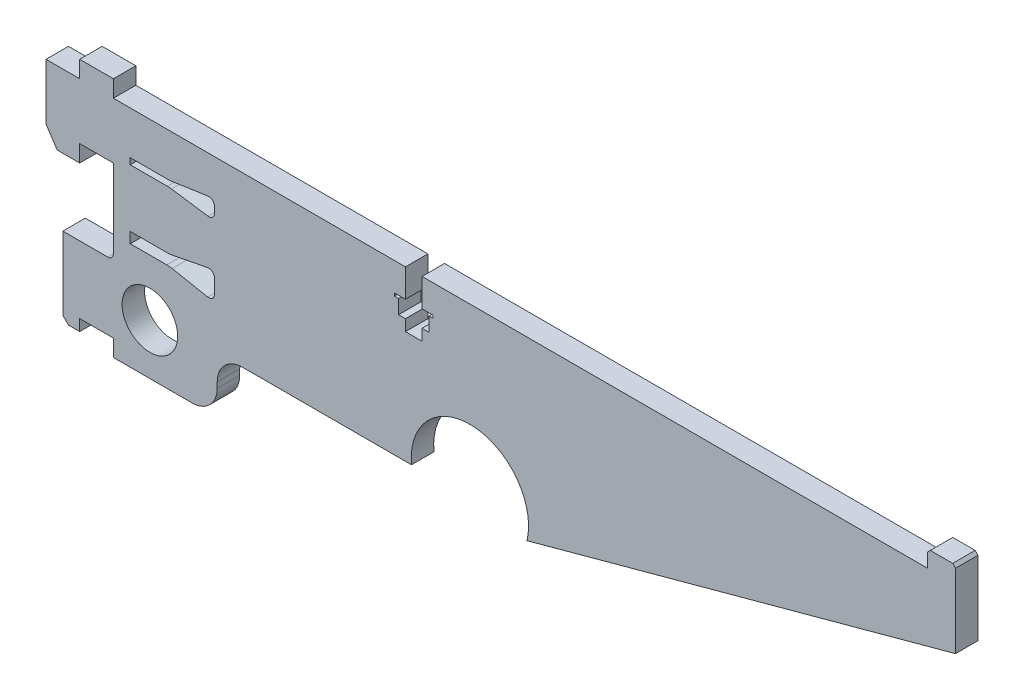
SolidWorks part; units mm, degrees
material "Oak"
ref_plane "Front Plane" through (0, 0, 0) normal (0, 0, 1) x (1, 0, 0)
ref_plane "Top Plane" through (0, 0, 0) normal (0, 1, 0) x (1, 0, 0)
ref_plane "Right Plane" through (0, 0, 0) normal (1, 0, 0) x (0, 0, -1)
sketch "Sketch1" plane through (0, 0, 0) normal (0, 0, 1) x (1, 0, 0)
  line L0 (7.5, -7) -> (16.5, -7)
  line L1 (16.5, -7) -> (16.5, 8)
  line L2 (16.5, 8) -> (10.5, 8)
  line L3 (10.5, 8) -> (10.5, 5)
  line L4 (10.5, 5) -> (4.5, 5)
  line L5 (4.5, 5) -> (4.5, 18)
  line L6 (4.5, 18) -> (10.5, 18)
  line L7 (166.5, 21) -> (166.5, 7.3204)
  line L8 (72.4558, -18.231) -> (90.1661, -13.4192) construction
  line L9 (10.5, -21) -> (7.5, -21)
  line L10 (-18, 24.8801) -> (-18, -27.1715) construction
  line L11 (10.5, 18) -> (10.5, 21)
  line L12 (10.5, 21) -> (16.5, 21)
  line L13 (19.5, -2) -> (34.5, -2) construction
  line L14 (19.5, -2.95) -> (19.5, -1.05)
  line L15 (19.5, -1.05) -> (26.5, -1.05)
  line L16 (26.5, -1.05) -> (34.5, 0.5)
  line L17 (34.5, 0.5) -> (34.5, -4.5)
  line L18 (26.5, -2.95) -> (34.5, -4.5)
  line L19 (19.5, -2.95) -> (26.5, -2.95)
  line L20 (19.5, -13) -> (34.5, -13) construction
  line L21 (19.5, -16.5) -> (19.5, -9.5) construction
  line L22 (19.5, -9.5) -> (34.5, -9.5) construction
  line L23 (16.5, -22) -> (16.5, -19)
  line L24 (34.5, -9.5) -> (34.5, -16.5) construction
  line L25 (16.5, -19) -> (10.5, -19)
  line L26 (19.5, -16.5) -> (34.5, -16.5) construction
  line L27 (90.1661, -13.4192) -> (166.5, 7.3204)
  line L28 (80, -11) -> (81.311, -15.8251) construction
  line L30 (70, 18) -> (70, 8) construction
  line L31 (68.52, 18) -> (68.52, 13)
  line L32 (68.52, 13) -> (66.55, 13)
  line L33 (66.55, 13) -> (66.55, 12.5)
  line L34 (66.55, 12.5) -> (67.3, 12.5)
  line L35 (67.3, 12.5) -> (67.3, 10)
  line L36 (67.3, 10) -> (68.52, 10)
  line L37 (68.52, 10) -> (68.52, 8)
  line L38 (68.52, 8) -> (71.48, 8)
  line L39 (71.48, 10) -> (71.48, 8)
  line L40 (72.7, 10) -> (71.48, 10)
  line L41 (72.7, 12.5) -> (72.7, 10)
  line L42 (73.45, 12.5) -> (72.7, 12.5)
  line L44 (13.5, 8) -> (13.5, -7) construction
  line L45 (16.5, 21) -> (16.5, 18)
  line L46 (16.5, 18) -> (68.52, 18)
  line L47 (7.5, -21) -> (7.5, -7)
  line L49 (16.5, -22) -> (58.5836, -22)
  line L50 (58.5836, -22) -> (72.4558, -18.231)
  line L51 (73.45, 13) -> (73.45, 12.5)
  line L52 (71.48, 13) -> (73.45, 13)
  line L53 (71.48, 18) -> (71.48, 13)
  line L54 (71.48, 18) -> (161.5, 18)
  line L57 (161.5, 18) -> (161.5, 21)
  line L58 (161.5, 21) -> (166.5, 21)
  line L59 (19.5, 9.7767) -> (34.5, 9.7767) construction
  line L60 (19.5, 9.2267) -> (19.5, 10.3267)
  line L61 (19.5, 10.3267) -> (26.5, 10.3267)
  line L62 (26.5, 10.3267) -> (34.5, 11.4876)
  line L63 (34.5, 11.4876) -> (34.5, 8.0658)
  line L64 (26.5, 9.2267) -> (34.5, 8.0658)
  line L65 (19.5, 9.2267) -> (26.5, 9.2267)
  line L66 (10.5, -19) -> (10.5, -21)
  line L67 (27, -2) -> (27, -13) construction
  circle A0 centre (0, 0) radius 6 construction
  circle A1 centre (80, -11) radius 6 construction
  arc A2 (90.1661, -13.4192) -> (72.4558, -18.231) centre (80, -11) ccw
  circle A3 centre (23, -13) radius 3.5 construction
  circle A4 centre (23, -13) radius 4.9497
  point P76 (27, -7.5)
  dimension "D1" = 12
  dimension "D7" = 11
  dimension "D23" = 20.9
  dimension "D3" = 6
  dimension "D4" = 10.5
  dimension "D5" = 80
  dimension "D6" = 18
  dimension "D8" = 156
  dimension "D9" = 15
  dimension "D10" = 8
  dimension "D11" = 3
  dimension "D12" = 15
  dimension "D13" = 1.9
  dimension "D14" = 3
  dimension "D15" = 7
  dimension "D16" = 15
  dimension "D17" = 5
  dimension "D18" = 7.5
  dimension "D19" = 1.1
  dimension "D20" = 7
  dimension "D21" = 11
  dimension "D22" = 28.5
  dimension "D24" = 5
  dimension "D26" = 2
  dimension "D27" = 10
  dimension "D28" = 2
  dimension "D29" = 0.5
  dimension "D30" = 2.5
  dimension "D31" = 2.96
  dimension "D32" = 3
  dimension "D33" = 6.9
  dimension "D34" = 5.4
  dimension "D35" = 53.5
  dimension "D36" = 5
  dimension "D37" = 3
extrude "Boss-Extrude1" add sketch "Sketch1" along normal blind 4
chamfer "Chamfer1" distance 3 distance2 2 1 edges at (4.5, 5, 2) first distance on face at (4.5, 11.5, 2)
fillet "Fillet1" radius 1 4 edges at (34.5, -4.5, 2) (34.5, 0.5, 2) (34.5, 8.0658, 2) (34.5, 11.4876, 2)
fillet "Fillet2" radius 5 4 edges at (26.5, -1.05, 2) (26.5, -2.95, 2) (26.5, 9.2267, 2) (26.5, 10.3267, 2)
chamfer "Chamfer2" distance 0.5 angle 45 2 edges at (166.5, 21, 2) (161.5, 21, 2)
chamfer "Chamfer3" distance 1 distance2 1 1 edges at (7.5, -21, 2)
fillet "Fillet3" radius 1 1 edges at (16.5, -7, 2)
sketch "Sketch2" plane through (0, 0, 4) normal (0, 0, 1) x (1, 0, 0)
  line L0 (16.5, -22) -> (58.5836, -22) construction
  line L1 (35, -22) -> (79.3647, -22)
  line L2 (35, -22) -> (35, -12)
  line L3 (35, -12) -> (79.3647, -12)
  line L4 (79.3647, -22) -> (79.3647, -12)
  line L5 (16.5, 8) -> (16.5, -6) construction
  dimension "D1" = 10
  dimension "D2" = 18.5
extrude "Cut-Extrude1" cut sketch "Sketch2" against normal through all
fillet "Fillet4" radius 4.5 2 edges at (35, -12, 2) (35, -22, 2)
equation "\"bed-plate-thickness\"=3"
equation "\"D1@Boss-Extrude1\"=\"y-cross-rib-thickness\""
equation "\"D3@Sketch1\"=\"y-rib-thickness\""
equation "\"D37@Sketch1\"=\"bed-plate-thickness\""
equation "\"y-cross-rib-thickness\"=4"
equation "\"y-rib-thickness\"=6"
equation "\"x-plate-thickness\"=5"
equation "\"rod-diameter\"=12"
equation "\"t-nut-hole-diameter\"=3"
